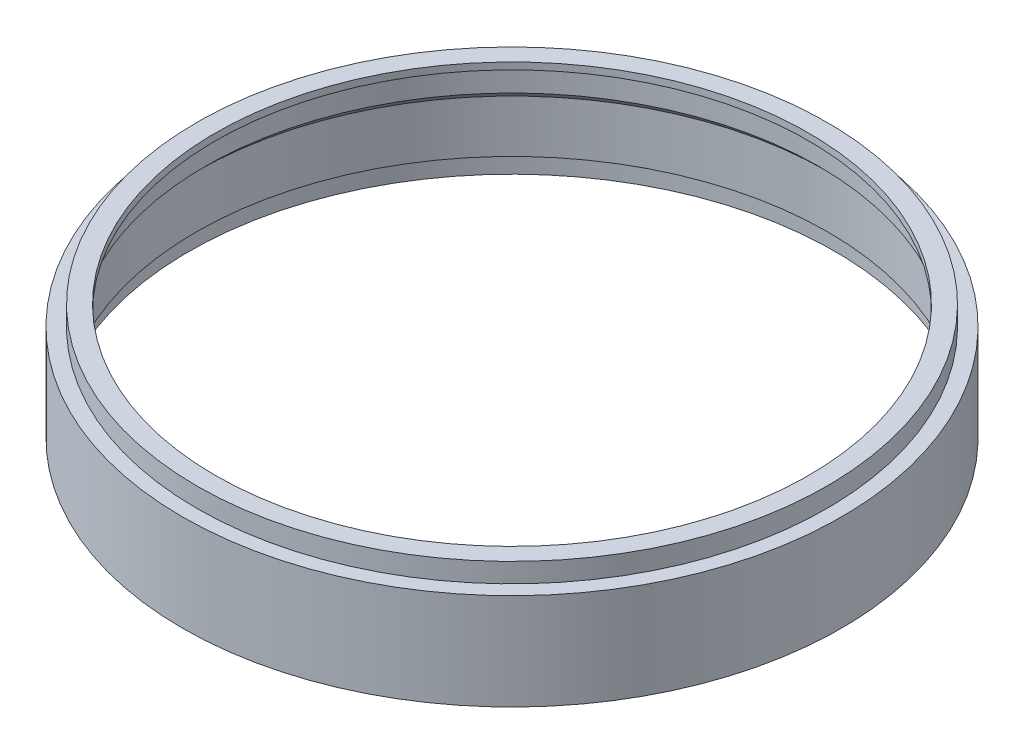
SolidWorks part; units mm, degrees
ref_plane "Front Plane" through (0, 0, 0) normal (0, 0, 1) x (1, 0, 0)
ref_plane "Top Plane" through (0, 0, 0) normal (0, 1, 0) x (1, 0, 0)
ref_plane "Right Plane" through (0, 0, 0) normal (1, 0, 0) x (0, 0, -1)
ref_axis "Axis1" through (0, 0, 0) along (0, 1, 0)
sketch "Sketch1" plane through (0, 0, 0) normal (0, 0, 1) x (1, 0, 0)
  line L0 (0, 0) -> (0, -50000) construction
  line L1 (-48.35, 0) -> (-48.35, 14.15)
  line L2 (-48.35, 0) -> (-47.4, 0)
  line L3 (-47.4, 0) -> (-47.4, 3)
  line L4 (-47.4, 3) -> (-46.35, 3)
  line L5 (-46.35, 3) -> (-46.35, 10.67)
  line L7 (-48.35, 0) -> (-48.35, -9.6235) construction
  line L8 (-46.35, 10.67) -> (-45.02, 12)
  line L10 (-45.02, 12) -> (-45.02, 16)
  line L11 (-45.02, 16) -> (-43.52, 16)
  line L12 (-47.35, 3) -> (-47.35, 0) construction
  line L13 (-46.35, 3) -> (-46.35, -7.15) construction
  line L14 (-45, 16.65) -> (-45, 12.65) construction
  line L17 (-43.52, 16) -> (-43.52, 17)
  line L26 (-46.22, 17) -> (-46.22, 14.15)
  line L27 (-46.22, 14.15) -> (-48.35, 14.15)
  line L31 (46.35, 3) -> (-46.35, 3) construction
  line L32 (-46.22, 17) -> (-43.52, 17)
  line L34 (-48.35, 15.15) -> (48.35, 15.15) construction
  dimension "D1" = 135
  dimension "D2" = 0.02
  dimension "D3" = 1.2
  dimension "D4" = 1.5
  dimension "D5" = 1
  dimension "D6" = 0.05
  dimension "D7" = 4
  dimension "D8" = 1
revolve "Revolve1" add sketch "Sketch1" angle 360 about L0
